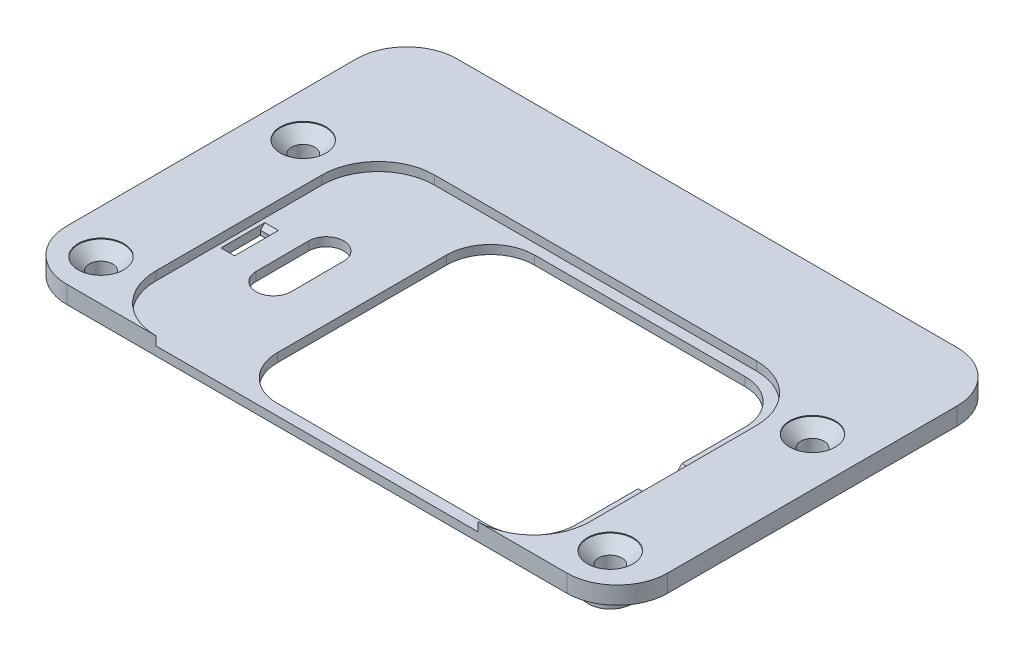
SolidWorks part; units mm, degrees
ref_plane "前视基准面" through (0, 0, 0) normal (0, 0, 1) x (1, 0, 0)
ref_plane "上视基准面" through (0, 0, 0) normal (0, 1, 0) x (1, 0, 0)
ref_plane "右视基准面" through (0, 0, 0) normal (1, 0, 0) x (0, 0, -1)
other "Configuration Table"
sketch "草图1" plane through (0, 0, 0) normal (0, 1, 0) x (1, 0, 0)
  line L1 (-10.0242, 18.5386) -> (58.4758, 18.5386)
  line L2 (-10.0242, 18.5386) -> (-10.0242, -25.9614)
  line L3 (-10.0242, -25.9614) -> (58.4758, -25.9614)
  line L4 (58.4758, 18.5386) -> (58.4758, -25.9614)
  dimension "D1" = 68.5
  dimension "D2" = 44.5
extrude "凸台-拉伸1" add sketch "草图1" along normal blind 2
fillet "圆角1" radius 5.75 4 edges at (-10.0242, 1, -18.5386) (58.4758, 1, -18.5386) (58.4758, 1, 25.9614) (-10.0242, 1, 25.9614)
sketch "草图3" plane through (0, 2, 0) normal (0, 1, 0) x (1, 0, 0)
  line L0 (58.4758, -20.2114) -> (58.4758, 12.7886) construction
  line L1 (5.8758, 5.7886) -> (42.5758, 5.7886)
  line L2 (-0.5242, -0.6114) -> (-0.5242, -19.5614)
  line L3 (5.8758, -25.9614) -> (42.5758, -25.9614)
  line L4 (48.9758, -0.6114) -> (48.9758, -19.5614)
  line L5 (-10.0242, 12.7886) -> (-10.0242, -20.2114) construction
  line L6 (52.7258, 18.5386) -> (-4.2742, 18.5386) construction
  arc A0 (42.5758, 5.7886) -> (48.9758, -0.6114) centre (42.5758, -0.6114) cw
  arc A1 (42.5758, -25.9614) -> (48.9758, -19.5614) centre (42.5758, -19.5614) ccw
  arc A2 (-0.5242, -19.5614) -> (5.8758, -25.9614) centre (5.8758, -19.5614) ccw
  arc A3 (5.8758, 5.7886) -> (-0.5242, -0.6114) centre (5.8758, -0.6114) ccw
  point P12 (48.9758, -25.9614)
  point P15 (-0.5242, -25.9614)
  dimension "D3" = 6.4
  dimension "D1" = 9.5
  dimension "D2" = 9.5
  dimension "D4" = 31.75
  dimension "D5" = 12.75
extrude "切除-拉伸1" cut sketch "草图3" against normal blind 1
sketch "草图4" plane through (0, 1, 0) normal (0, 1, 0) x (1, 0, 0)
  line L0 (58.4758, -20.2114) -> (58.4758, 12.7886) construction
  line L1 (42.4758, -24.7114) -> (18.4758, -24.7114)
  line L2 (47.4758, -19.7114) -> (47.4758, -0.4114)
  line L3 (42.4758, 4.5886) -> (18.4758, 4.5886)
  line L4 (13.4758, -19.7114) -> (13.4758, -0.4114)
  line L6 (-4.2742, -26.2114) -> (52.7258, -26.2114) construction
  arc A0 (47.4758, -0.4114) -> (42.4758, 4.5886) centre (42.4758, -0.4114) ccw
  arc A1 (42.4758, -24.7114) -> (47.4758, -19.7114) centre (42.4758, -19.7114) ccw
  arc A2 (18.4758, 4.5886) -> (13.4758, -0.4114) centre (18.4758, -0.4114) ccw
  arc A3 (18.4758, -24.7114) -> (13.4758, -19.7114) centre (18.4758, -19.7114) cw
  point P10 (47.4758, 4.5886)
  point P13 (47.4758, -24.7114)
  point P18 (13.4758, -24.7114)
  dimension "D5" = 5
  dimension "D1" = 29.3
  dimension "D2" = 34
  dimension "D3" = 11
  dimension "D4" = 1.5
extrude "切除-拉伸2" cut sketch "草图4" against normal blind 1
sketch "草图5" plane through (0, 2, 0) normal (0, 1, 0) x (1, 0, 0)
  circle A0 centre (53.0008, -21.2864) radius 1.325
  circle A1 centre (53.0008, 1.7636) radius 1.325
  circle A2 centre (-5.0492, 1.7636) radius 1.325
  circle A3 centre (-5.0492, -21.2864) radius 1.325
  dimension "D1" = 2.65
extrude "切除-拉伸3" cut sketch "草图5" against normal up to next
sketch "草图6" plane through (0, 2, 0) normal (0, 1, 0) x (1, 0, 0)
  circle A0 centre (-5.0492, 1.7636) radius 2.6
  circle A1 centre (-5.0492, -21.2864) radius 2.6
  circle A2 centre (53.0008, 1.7636) radius 2.6
  circle A3 centre (53.0008, -21.2864) radius 2.6
  dimension "D1" = 5.2
sketch "草图7" plane through (0, 1, 0) normal (0, 1, 0) x (1, 0, 0)
  line L0 (6.2263, -6.8945) -> (6.2448, -12.9027) construction
  line L1 (8.2263, -6.8884) -> (8.2448, -12.8965)
  line L2 (4.2263, -6.9007) -> (4.2448, -12.9088)
  arc A0 (8.2263, -6.8884) -> (4.2263, -6.9007) centre (6.2263, -6.8945) ccw
  arc A1 (4.2448, -12.9088) -> (8.2448, -12.8965) centre (6.2448, -12.9027) ccw
  point P4 (6.2355, -9.8986)
  dimension "D1" = 2
extrude "切除-拉伸5" cut sketch "草图7" against normal through all
extrude "切除-拉伸6" cut sketch "草图6" against normal blind 1.5
chamfer "倒角2" distance 1.4 angle 45 4 edges at (53.0008, 0.5, 23.8864) (-5.0492, 0.5, 23.8864) (-5.0492, 0.5, 0.8364) (53.0008, 0.5, 0.8364)
sketch "草图8" plane through (0, 0, 0) normal (0, -1, 0) x (1, 0, 0)
  circle A0 centre (-5.0492, 21.2864) radius 2.5
  circle A1 centre (-5.0492, -1.7636) radius 2.5
  circle A2 centre (53.0008, 21.2864) radius 2.5
  circle A3 centre (53.0008, -1.7636) radius 2.5
  dimension "D1" = 5
extrude "凸台-拉伸2" add sketch "草图8" along normal blind 2
sketch "草图9" plane through (0, 0, 0) normal (0, 1, 0) x (1, 0, 0)
  circle A0 centre (53.0008, -21.2864) radius 1.325 construction
  circle A1 centre (53.0008, 1.7636) radius 1.325 construction
  circle A2 centre (-5.0492, 1.7636) radius 1.325 construction
  circle A3 centre (-5.0492, -21.2864) radius 1.325 construction
  circle A4 centre (53.0008, -21.2864) radius 1.325
  circle A5 centre (53.0008, 1.7636) radius 1.325
  circle A6 centre (-5.0492, 1.7636) radius 1.325
  circle A7 centre (-5.0492, -21.2864) radius 1.325
extrude "切除-拉伸7" cut sketch "草图9" against normal through all
sketch "草图10" plane through (0, 1, 0) normal (0, 1, 0) x (1, 0, 0)
  line L0 (47.4758, -8.0864) -> (48.5258, -8.0864) construction
  line L1 (0.9758, -8.0864) -> (-0.0742, -8.0864)
  line L2 (0.9758, -8.0864) -> (0.9758, -12.0864)
  line L3 (0.9758, -12.0864) -> (-0.0742, -12.0864)
  line L4 (-0.0742, -8.0864) -> (-0.0742, -12.0864)
  line L5 (47.4758, -8.0864) -> (48.5258, -8.0864)
  line L6 (47.4758, -8.0864) -> (47.4758, -12.0864)
  line L7 (47.4758, -12.0864) -> (48.5258, -12.0864)
  line L8 (48.5258, -8.0864) -> (48.5258, -12.0864)
  line L12 (47.4758, -19.7114) -> (47.4758, -0.4114) construction
extrude "切除-拉伸8" cut sketch "草图10" against normal through all
chamfer "倒角3" distance 0.5 angle 45 5 edges at (0.4508, 1, 12.0864) (0.9758, 1, 10.0864) (0.4508, 1, 8.0864) (48.0008, 1, 8.0864) (48.0008, 1, 12.0864)
